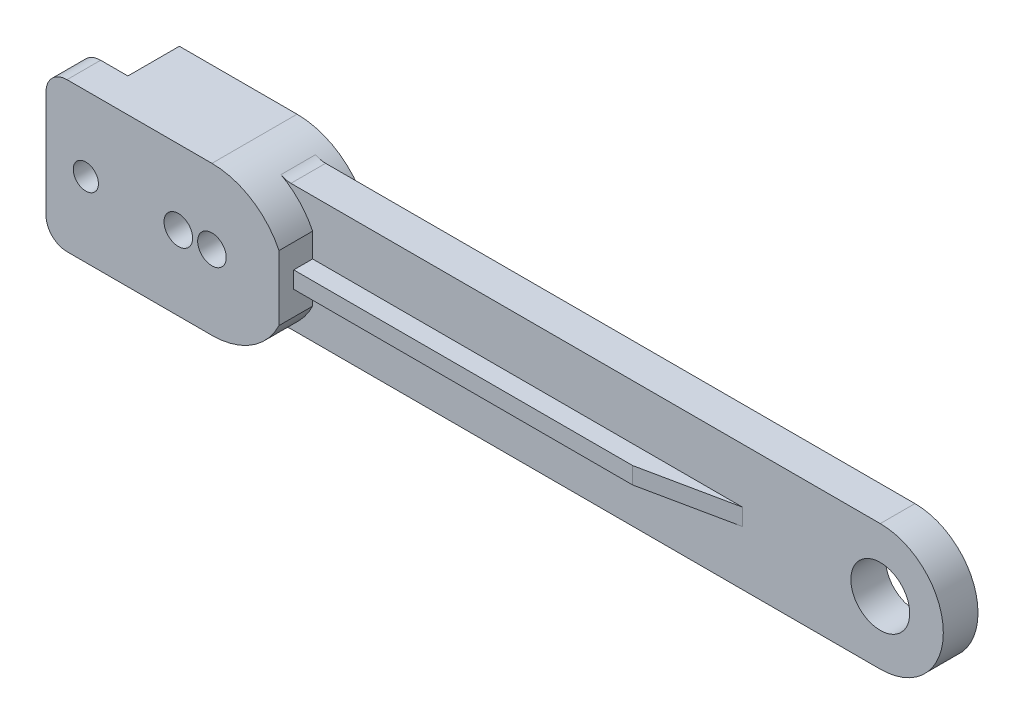
SolidWorks part; units mm, degrees
ref_plane "Front Plane" through (0, 0, 0) normal (0, 0, 1) x (1, 0, 0)
ref_plane "Top Plane" through (0, 0, 0) normal (0, 1, 0) x (1, 0, 0)
ref_plane "Right Plane" through (0, 0, 0) normal (1, 0, 0) x (0, 0, -1)
sketch "Sketch1" plane through (0, 0, 0) normal (0, 0, 1) x (1, 0, 0)
  line L0 (0, 0) -> (14, 0)
  line L1 (14, 7.725) -> (0, 7.725)
  line L2 (0, 7.725) -> (0, 12.725)
  line L3 (0, 12.725) -> (14, 12.725)
  line L4 (14, -5) -> (0, -5)
  line L5 (0, -5) -> (0, 0)
  arc A0 (14, 0) -> (14, 7.725) centre (14, 3.8625) ccw
  arc A1 (14, 12.725) -> (14, -5) centre (14, 3.8625) cw
  dimension "D1" = 7.725
  dimension "D2" = 14
  dimension "D3" = 5
extrude "Boss-Extrude1" add sketch "Sketch1" along normal blind 4.125
sketch "Sketch2" plane through (0, 0, 0) normal (0, 0, -1) x (-1, 0, 0)
  line L5 (-14, 6.675) -> (0, 6.675)
  line L6 (0, -5) -> (0, 0)
  line L7 (0, 0) -> (-14, 0)
  line L8 (-14, 7.725) -> (0, 7.725)
  line L9 (0, 7.725) -> (0, 12.725)
  line L10 (0, 12.725) -> (-14, 12.725)
  line L11 (-14, -5) -> (0, -5)
  line L12 (0, -5) -> (0, 0)
  line L15 (0, 7.725) -> (0, 12.725)
  line L16 (0, 12.725) -> (-14, 12.725)
  line L17 (-14, -5) -> (0, -5)
  line L18 (0, 6.675) -> (0, 7.725)
  line L19 (-14, 1.05) -> (0, 1.05)
  line L20 (0, 1.05) -> (0, 0)
  arc A1 (-14, 6.675) -> (-14, 1.05) centre (-14, 3.8625) ccw
  arc A2 (-14, 7.725) -> (-14, 0) centre (-14, 3.8625) ccw
  arc A3 (-14, 12.725) -> (-14, -5) centre (-14, 3.8625) ccw
  arc A5 (-14, 12.725) -> (-14, -5) centre (-14, 3.8625) ccw
  dimension "D2" = 5.625
  dimension "D1" = 0
extrude "Boss-Extrude2" add sketch "Sketch2" along normal blind 2
sketch "Sketch3" plane through (0, 0, 4.125) normal (0, 0, 1) x (1, 0, 0)
  line L1 (0, 12.725) -> (-3.2389, 12.725)
  line L2 (-5.7389, 10.225) -> (-5.7389, -2.5)
  line L3 (-3.2389, -5) -> (0, -5)
  line L6 (0, 0) -> (0, -5)
  line L7 (0, -5) -> (14, -5)
  line L8 (14, 12.725) -> (0, 12.725)
  line L9 (0, 12.725) -> (0, 7.725)
  line L10 (0, 7.725) -> (14, 7.725)
  line L11 (14, 0) -> (0, 0)
  line L13 (0, -5) -> (14, -5)
  line L14 (14, 12.725) -> (0, 12.725)
  line L18 (21.9765, 7.725) -> (21.9765, 0)
  circle A0 centre (14, 3.8625) radius 1.7
  circle A1 centre (10, 3.8625) radius 1.7
  circle A2 centre (-1, 3.8625) radius 1.5
  arc A3 (21.9765, 7.725) -> (14, 12.725) centre (14, 3.8625) ccw
  arc A4 (14, -5) -> (14, 12.725) centre (14, 3.8625) ccw
  arc A5 (14, 0) -> (14, 7.725) centre (14, 3.8625) ccw
  arc A6 (14, -5) -> (21.9765, 0) centre (14, 3.8625) ccw
  arc A8 (-5.7389, -2.5) -> (-3.2389, -5) centre (-3.2389, -2.5) ccw
  arc A9 (-3.2389, 12.725) -> (-5.7389, 10.225) centre (-3.2389, 10.225) ccw
  dimension "D1" = 3.4
  dimension "D4" = 11
  dimension "D5" = 2.5
  dimension "D2" = 4
  dimension "D3" = 0
extrude "Boss-Extrude3" add sketch "Sketch3" along normal blind 4
sketch "Sketch4" plane through (0, 0, 0) normal (0, 0, 1) x (1, 0, 0)
  line L0 (89.5, 11.3625) -> (18.7216, 11.3625)
  line L1 (89.5, -3.6375) -> (18.7216, -3.6375)
  line L2 (-1, 3.8625) -> (49999, 3.8625) construction
  arc A0 (18.7216, -3.6375) -> (18.7216, 11.3625) centre (14, 3.8625) ccw
  circle A2 centre (-10.5, 3.8625) radius 2.9268 construction
  arc A4 (89.5, 11.3625) -> (89.5, -3.6375) centre (89.5, 3.8625) cw
  point P4 (18.7372, 11.3527)
  dimension "D2" = 100
  dimension "D1" = 15
extrude "Boss-Extrude4" add sketch "Sketch4" along normal up to surface (4.125 mm away) up to face at (22.4195, 3.8625, 4.125)
ref_plane "Plane1" through (0, 3.8625, 0) normal (0, 1, 0) x (1, 0, 0)
fillet "Fillet2" radius 2.5 2 edges at (18.7216, 11.3625, 2.0625) (18.7216, -3.6375, 2.0625)
sketch "Sketch6" plane through (0, 3.8625, 0) normal (0, 1, 0) x (1, 0, 0)
  line L21 (62.2997, -6.3733) -> (73.1167, -4.125)
  line L22 (21.9765, -4.125) -> (60.3227, -4.125)
  line L23 (21.9765, -4.125) -> (21.9765, -6.3733)
  line L24 (21.9765, -6.3733) -> (62.2997, -6.3733)
  line L26 (89.5, -4.125) -> (19.395, -4.125) construction
  line L27 (60.3227, -4.125) -> (73.1167, -4.125)
  line L28 (22.8625, 2) -> (14, 2) construction
  line L29 (21.9765, 2) -> (62.2997, 2)
  line L30 (21.9765, 2) -> (21.9765, 0)
  line L31 (21.9765, 0) -> (73.1167, 0)
  line L33 (89.5, 0) -> (19.395, 0) construction
  line L34 (62.2997, 2) -> (73.1167, 0)
  point P16 (73.1167, 0)
extrude "Boss-Extrude8" add sketch "Sketch6" along normal mid plane 2
sketch "Sketch9" plane through (0, 0, 4.125) normal (0, 0, 1) x (1, 0, 0)
  circle A0 centre (89.5, 3.8625) radius 3.5
  dimension "D1" = 7
extrude "Cut-Extrude1" cut sketch "Sketch9" against normal through all
